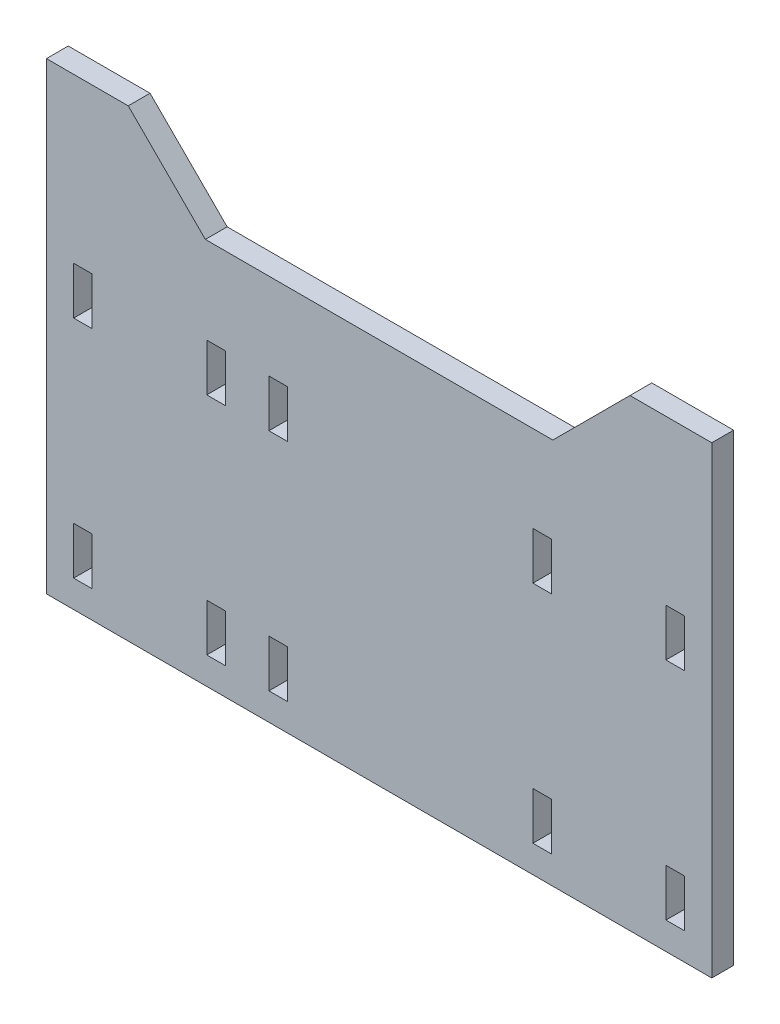
SolidWorks part; units mm, degrees
ref_plane "Front Plane" through (0, 0, 0) normal (0, 0, 1) x (1, 0, 0)
ref_plane "Top Plane" through (0, 0, 0) normal (0, 1, 0) x (1, 0, 0)
ref_plane "Right Plane" through (0, 0, 0) normal (1, 0, 0) x (0, 0, -1)
sketch "Sketch1" plane through (0, 0, 0) normal (0, 0, 1) x (1, 0, 0)
  line L0 (0, 66.0849) -> (0, -70.4198) construction
  line L6 (-37.3, 25) -> (-33.9, 25)
  line L7 (22.5, 25) -> (25.9, 25)
  line L8 (22.5, 25) -> (22.5, 16.3)
  line L9 (22.5, 16.3) -> (25.9, 16.3)
  line L10 (25.9, 25) -> (25.9, 16.3)
  line L11 (-103.5149, 0) -> (102.2922, 0) construction
  line L12 (22.5, -16.3) -> (25.9, -16.3)
  line L13 (22.5, -25) -> (22.5, -16.3)
  line L14 (25.9, -25) -> (25.9, -16.3)
  line L15 (22.5, -25) -> (25.9, -25)
  line L16 (-22.5, 25) -> (-25.9, 25)
  line L17 (-22.5, 25) -> (-22.5, 16.3)
  line L18 (-25.9, 25) -> (-25.9, 16.3)
  line L19 (-22.5, 16.3) -> (-25.9, 16.3)
  line L20 (-22.5, -16.3) -> (-25.9, -16.3)
  line L21 (-22.5, -25) -> (-22.5, -16.3)
  line L22 (-25.9, -25) -> (-25.9, -16.3)
  line L23 (-22.5, -25) -> (-25.9, -25)
  line L36 (55.3, 30) -> (55.3, -30)
  line L39 (46.9, 25) -> (50.3, 25)
  line L40 (46.9, 25) -> (46.9, 16.3)
  line L41 (46.9, 16.3) -> (50.3, 16.3)
  line L42 (50.3, 25) -> (50.3, 16.3)
  line L43 (46.9, -16.3) -> (50.3, -16.3)
  line L44 (46.9, -16.3) -> (46.9, -25)
  line L45 (46.9, -25) -> (50.3, -25)
  line L46 (50.3, -16.3) -> (50.3, -25)
  line L47 (-37.3, 25) -> (-37.3, 16.3)
  line L48 (-37.3, 16.3) -> (-33.9, 16.3)
  line L49 (-33.9, 25) -> (-33.9, 16.3)
  line L50 (-37.3, -16.3) -> (-33.9, -16.3)
  line L51 (-37.3, -16.3) -> (-37.3, -25)
  line L52 (-37.3, -25) -> (-33.9, -25)
  line L53 (-33.9, -16.3) -> (-33.9, -25)
  line L57 (-66.7, 30) -> (-66.7, -30)
  line L59 (-66.7, 30) -> (55.3, 30)
  line L60 (-61.7, 25) -> (-58.3, 25)
  line L61 (-61.7, 25) -> (-61.7, 16.3)
  line L62 (-61.7, 16.3) -> (-58.3, 16.3)
  line L63 (-58.3, 25) -> (-58.3, 16.3)
  line L64 (-61.7, -16.3) -> (-58.3, -16.3)
  line L65 (-61.7, -16.3) -> (-61.7, -25)
  line L66 (-61.7, -25) -> (-58.3, -25)
  line L67 (-58.3, -16.3) -> (-58.3, -25)
  line L68 (-66.7, -30) -> (55.3, -30)
  point P0 (0, 0)
  dimension "D2" = 60
  dimension "D3" = 8
  dimension "D4" = 122
  dimension "D5" = 3.4
  dimension "D6" = 8.7
  dimension "D7" = 45
  dimension "D8" = 21
  dimension "D9" = 21
  dimension "D10" = 5
  dimension "D12" = 5
extrude "Boss-Extrude1" add sketch "Sketch1" along normal blind 4
sketch "Sketch2" plane through (0, 0, 0) normal (0, 0, 1) x (1, 0, 0)
  line L0 (-66.7, 30) -> (-66.7, 55)
  line L1 (-66.7, 55) -> (-51.7, 55)
  line L2 (-51.7, 55) -> (-37.5579, 40.8579)
  line L7 (55.3, 30) -> (-66.7, 30)
  line L8 (40.3, 55) -> (55.3, 55)
  line L9 (55.3, 55) -> (55.3, 30)
  line L10 (40.3, 55) -> (26.1579, 40.8579)
  line L11 (26.1579, 40.8579) -> (-37.5579, 40.8579)
  dimension "D1" = 25
  dimension "D2" = 15
  dimension "D3" = 135
  dimension "D4" = 20
extrude "Boss-Extrude2" add sketch "Sketch2" along normal blind 4
